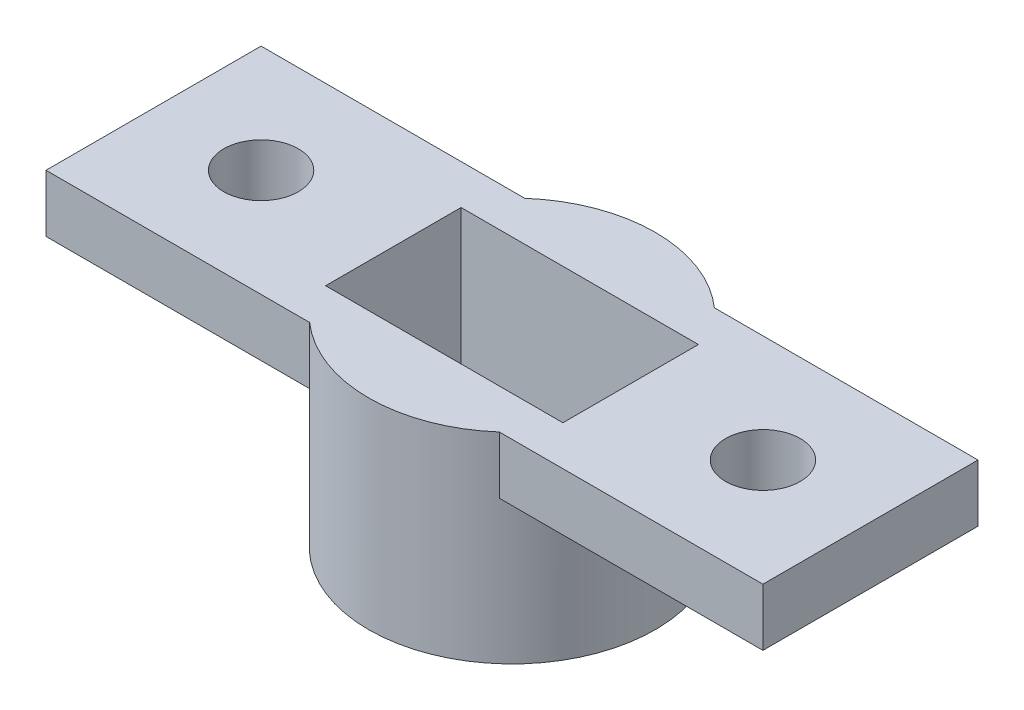
SolidWorks part; units mm, degrees
ref_plane "Front Plane" through (0, 0, 0) normal (0, 0, 1) x (1, 0, 0)
ref_plane "Top Plane" through (0, 0, 0) normal (0, 1, 0) x (1, 0, 0)
ref_plane "Right Plane" through (0, 0, 0) normal (1, 0, 0) x (0, 0, -1)
sketch "Sketch1" plane through (0, 0, 0) normal (0, 1, 0) x (1, 0, 0)
  line L0 (-15.875, 0) -> (15.875, 0) construction
  line L1 (-5.255, -3) -> (5.255, -3)
  line L2 (-5.255, -3) -> (-5.255, 3)
  line L3 (-5.255, 3) -> (5.255, 3)
  line L4 (5.255, -3) -> (5.255, 3)
  line L5 (-5.255, -3) -> (5.255, 3) construction
  line L6 (-5.255, 3) -> (5.255, -3) construction
  line L7 (15.875, -4.7625) -> (-15.875, -4.7625)
  line L8 (15.875, -4.7625) -> (15.875, 4.7625)
  line L9 (15.875, 4.7625) -> (-15.875, 4.7625)
  line L10 (-15.875, -4.7625) -> (-15.875, 4.7625)
  line L11 (15.875, -4.7625) -> (-15.875, 4.7625) construction
  line L12 (15.875, 4.7625) -> (-15.875, -4.7625) construction
  line L13 (0, -4.7625) -> (0, 4.7625) construction
  circle A0 centre (0, 0) radius 6.35 construction
  circle A1 centre (11.1125, 0) radius 1.651
  circle A2 centre (-11.1125, 0) radius 1.651
  point P0 (0, 0)
  point P6 (0, 0)
  dimension "D3" = 12.7
  dimension "D6" = 3.302
  dimension "D1" = 10.51
  dimension "D2" = 6
  dimension "D4" = 9.525
  dimension "D5" = 31.75
  dimension "D7" = 4.7625
extrude "Boss-Extrude1" add sketch "Sketch1" along normal blind 2.54
sketch "Sketch2" plane through (0, 2.54, 0) normal (0, 1, 0) x (1, 0, 0)
  line L4 (-15.875, -4.7625) -> (15.875, -4.7625)
  line L5 (-15.875, 4.7625) -> (-15.875, -4.7625)
  line L6 (15.875, 4.7625) -> (-15.875, 4.7625)
  line L7 (15.875, -4.7625) -> (15.875, 4.7625)
  line L8 (-15.875, -4.7625) -> (15.875, -4.7625)
  line L9 (-15.875, 4.7625) -> (-15.875, -4.7625)
  line L10 (15.875, 4.7625) -> (-15.875, 4.7625)
  line L11 (15.875, -4.7625) -> (15.875, 4.7625)
  line L12 (-5.255, -3) -> (5.255, -3)
  line L13 (5.255, -3) -> (5.255, 3)
  line L14 (5.255, 3) -> (-5.255, 3)
  line L15 (-5.255, 3) -> (-5.255, -3)
  line L16 (-5.255, -3) -> (5.255, -3)
  line L17 (5.255, -3) -> (5.255, 3)
  line L18 (5.255, 3) -> (-5.255, 3)
  line L19 (-5.255, 3) -> (-5.255, -3)
  circle A1 centre (0, 0) radius 6.35 construction
  circle A2 centre (-11.1125, 0) radius 1.651
  circle A3 centre (-11.1125, 0) radius 1.651
  circle A4 centre (11.1125, 0) radius 1.651
  circle A5 centre (11.1125, 0) radius 1.651
  circle A6 centre (0, 0) radius 6.35
  line M26 (-5.255, 3) -> (5.255, 3)
  line M27 (5.255, 3) -> (5.255, -3)
  line M28 (5.255, -3) -> (-5.255, -3)
  line M29 (-5.255, -3) -> (-5.255, 3)
  dimension "D1" = 0
  dimension "D2" = 0
  dimension "D3" = 0
  dimension "D4" = 0
extrude "Boss-Extrude2" add sketch "Sketch2" against normal blind 8.89 contours L10 A6 | L8 A6 L10 M29 M26 M27 M28 | L8 A6 region at (-6.1913, 2.54, 0) region at (0, 2.54, 5.4048) region at (0, 2.54, -5.4048)
